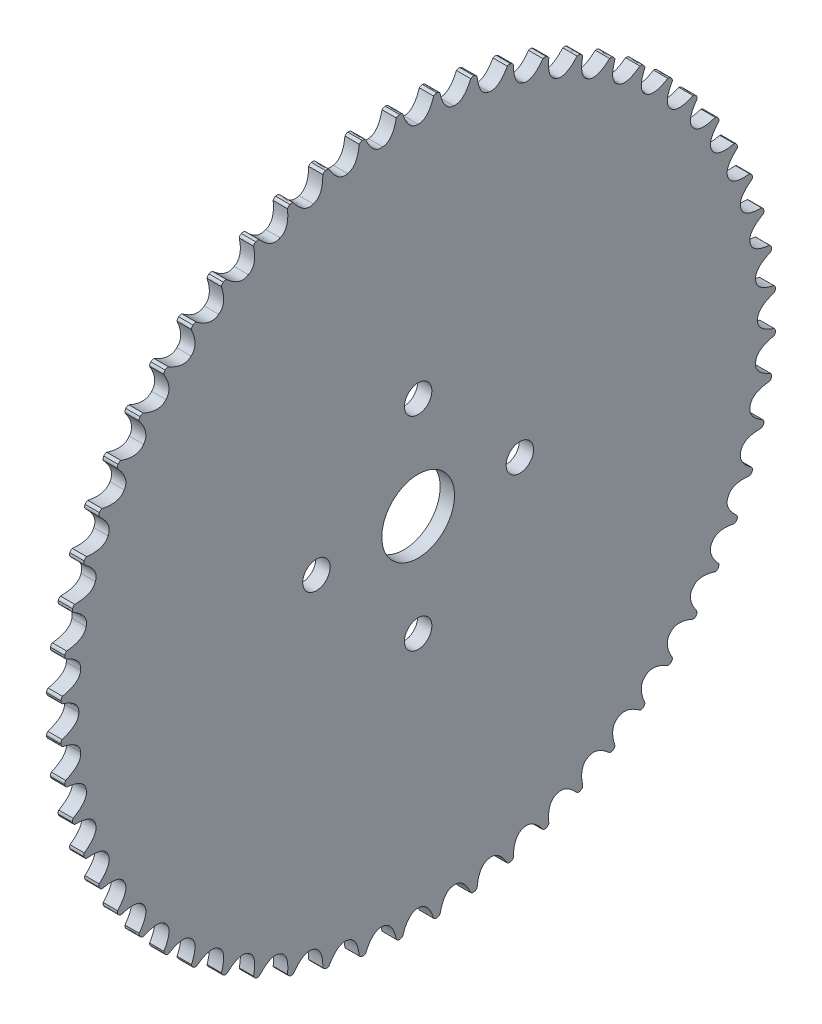
SolidWorks part; units mm, degrees
material "Cast Alloy Steel"
ref_plane "Front Plane" through (0, 0, 0) normal (0, 0, 1) x (1, 0, 0)
ref_plane "Top Plane" through (0, 0, 0) normal (0, 1, 0) x (1, 0, 0)
ref_plane "Right Plane" through (0, 0, 0) normal (1, 0, 0) x (0, 0, -1)
sketch "Sketch2" plane through (0, 0, 0) normal (1, 0, 0) x (0, 0, -1)
  line L3 (-20.5227, 123.2993) -> (-18.5833, 123.6065)
  line L4 (5.5611, 124.8719) -> (7.522, 124.7691)
  line L5 (-7.522, 124.7691) -> (-5.5611, 124.8719)
  line L7 (18.5833, 123.6065) -> (20.5227, 123.2993)
  line L8 (31.4019, 120.9869) -> (33.2986, 120.4787)
  line L9 (43.8765, 117.0417) -> (45.7096, 116.338)
  line L10 (55.8703, 111.8142) -> (57.6199, 110.9228)
  line L11 (67.252, 105.3616) -> (68.8988, 104.2922)
  line L12 (77.8969, 97.7547) -> (79.4229, 96.519)
  line L13 (87.6883, 89.0768) -> (89.0768, 87.6883)
  line L14 (96.519, 79.4229) -> (97.7547, 77.8969)
  line L15 (104.2922, 68.8988) -> (105.3616, 67.252)
  line L16 (110.9228, 57.6199) -> (111.8142, 55.8703)
  line L17 (116.338, 45.7096) -> (117.0417, 43.8765)
  line L18 (120.4787, 33.2986) -> (120.9869, 31.4019)
  line L19 (123.2993, 20.5227) -> (123.6065, 18.5833)
  line L20 (124.7691, 7.522) -> (124.8719, 5.5611)
  line L21 (124.8719, -5.5611) -> (124.7691, -7.522)
  line L22 (123.6065, -18.5833) -> (123.2993, -20.5227)
  line L23 (120.9869, -31.4019) -> (120.4787, -33.2986)
  line L24 (117.0417, -43.8765) -> (116.338, -45.7096)
  line L25 (111.8142, -55.8703) -> (110.9228, -57.6199)
  line L26 (105.3616, -67.252) -> (104.2922, -68.8988)
  line L27 (97.7547, -77.8969) -> (96.519, -79.4229)
  line L28 (89.0768, -87.6883) -> (87.6883, -89.0768)
  line L29 (79.4229, -96.519) -> (77.8969, -97.7547)
  line L30 (68.8988, -104.2922) -> (67.252, -105.3616)
  line L31 (57.6199, -110.9228) -> (55.8703, -111.8142)
  line L32 (45.7096, -116.338) -> (43.8765, -117.0417)
  line L33 (33.2986, -120.4787) -> (31.4019, -120.9869)
  line L34 (20.5227, -123.2993) -> (18.5833, -123.6065)
  line L35 (7.522, -124.7691) -> (5.5611, -124.8719)
  line L36 (-5.5611, -124.8719) -> (-7.522, -124.7691)
  line L37 (-18.5833, -123.6065) -> (-20.5227, -123.2993)
  line L38 (-31.4019, -120.9869) -> (-33.2986, -120.4787)
  line L39 (-43.8765, -117.0417) -> (-45.7096, -116.338)
  line L40 (-55.8703, -111.8142) -> (-57.6199, -110.9228)
  line L41 (-67.252, -105.3616) -> (-68.8988, -104.2922)
  line L42 (-77.8969, -97.7547) -> (-79.4229, -96.519)
  line L43 (-87.6883, -89.0768) -> (-89.0768, -87.6883)
  line L44 (-96.519, -79.4229) -> (-97.7547, -77.8969)
  line L45 (-104.2922, -68.8988) -> (-105.3616, -67.252)
  line L46 (-110.9228, -57.6199) -> (-111.8142, -55.8703)
  line L47 (-116.338, -45.7096) -> (-117.0417, -43.8765)
  line L48 (-120.4787, -33.2986) -> (-120.9869, -31.4019)
  line L49 (-123.2993, -20.5227) -> (-123.6065, -18.5833)
  line L50 (-124.7691, -7.522) -> (-124.8719, -5.5611)
  line L51 (-124.8719, 5.5611) -> (-124.7691, 7.522)
  line L52 (-123.6065, 18.5833) -> (-123.2993, 20.5227)
  line L53 (-120.9869, 31.4019) -> (-120.4787, 33.2986)
  line L54 (-117.0417, 43.8765) -> (-116.338, 45.7096)
  line L55 (-111.8142, 55.8703) -> (-110.9228, 57.6199)
  line L56 (-105.3616, 67.252) -> (-104.2922, 68.8988)
  line L57 (-97.7547, 77.8969) -> (-96.519, 79.4229)
  line L58 (-89.0768, 87.6883) -> (-87.6883, 89.0768)
  line L59 (-79.4229, 96.519) -> (-77.8969, 97.7547)
  line L60 (-68.8988, 104.2922) -> (-67.252, 105.3616)
  line L61 (-57.6199, 110.9228) -> (-55.8703, 111.8142)
  line L62 (-45.7096, 116.338) -> (-43.8765, 117.0417)
  line L63 (-33.2986, 120.4787) -> (-31.4019, 120.9869)
  line L65 (-20.5227, 123.2993) -> (-18.5833, 123.6065) [skipped]
  line L66 (5.5611, 124.8719) -> (7.522, 124.7691) [skipped]
  spline S6 degree 3 poles (-5.5611, 124.8719) (-4.8042, 122.3669) (-3.2326, 118.408) (0, 118.5697) knots 0 0 0 0 1 1 1 1
  spline S7 degree 3 poles (5.5611, 124.8719) (4.8042, 122.3669) (3.2326, 118.408) (0, 118.5697) knots 0 0 0 0 1 1 1 1
  spline S8 degree 3 poles (7.522, 124.7691) (8.0129, 122.1987) (9.1621, 118.0973) (12.3939, 117.9202) knots 0 0 0 0 1 1 1 1
  spline S9 degree 3 poles (18.5833, 123.6065) (17.5687, 121.1944) (15.5919, 117.4215) (12.3939, 117.9202) knots 0 0 0 0 1 1 1 1
  spline S10 degree 3 poles (20.5227, 123.2993) (20.7423, 120.6917) (21.4565, 116.4926) (24.652, 115.9787) knots 0 0 0 0 1 1 1 1
  spline S11 degree 3 poles (31.4019, 120.9869) (30.1407, 118.694) (27.7804, 115.1484) (24.652, 115.9787) knots 0 0 0 0 1 1 1 1
  spline S12 degree 3 poles (33.2986, 120.4787) (33.2444, 117.8624) (33.5157, 113.6116) (36.6401, 112.7665) knots 0 0 0 0 1 1 1 1
  spline S13 degree 3 poles (43.8765, 117.0417) (42.3825, 114.8932) (39.6645, 111.6138) (36.6401, 112.7665) knots 0 0 0 0 1 1 1 1
  spline S14 degree 3 poles (45.7096, 116.338) (45.3822, 113.7418) (45.2078, 109.4859) (48.2266, 108.3188) knots 0 0 0 0 1 1 1 1
  spline S15 degree 3 poles (55.8703, 111.8142) (54.16, 109.8337) (51.114, 106.8563) (48.2266, 108.3188) knots 0 0 0 0 1 1 1 1
  spline S16 degree 3 poles (57.6199, 110.9228) (57.0229, 108.3749) (56.4045, 104.1606) (59.2848, 102.6844) knots 0 0 0 0 1 1 1 1
  spline S17 degree 3 poles (67.252, 105.3616) (65.344, 103.5707) (62.0035, 100.9281) (59.2848, 102.6844) knots 0 0 0 0 1 1 1 1
  spline S18 degree 3 poles (68.8988, 104.2922) (68.0387, 101.8207) (66.9833, 97.6942) (69.6935, 95.9249) knots 0 0 0 0 1 1 1 1
  spline S19 degree 3 poles (77.8969, 97.7547) (75.8122, 96.173) (72.2137, 93.894) (69.6935, 95.9249) knots 0 0 0 0 1 1 1 1
  spline S20 degree 3 poles (79.4229, 96.519) (78.3092, 94.151) (76.8281, 90.1573) (79.3386, 88.1145) knots 0 0 0 0 1 1 1 1
  spline S21 degree 3 poles (87.6883, 89.0768) (85.4497, 87.7217) (81.6327, 85.8313) (79.3386, 88.1145) knots 0 0 0 0 1 1 1 1
  spline S22 degree 3 poles (89.0768, 87.6883) (87.7217, 85.4497) (85.8313, 81.6327) (88.1145, 79.3386) knots 0 0 0 0 1 1 1 1
  spline S23 degree 3 poles (96.519, 79.4229) (94.151, 78.3092) (90.1573, 76.8281) (88.1145, 79.3386) knots 0 0 0 0 1 1 1 1
  spline S24 degree 3 poles (97.7547, 77.8969) (96.173, 75.8122) (93.894, 72.2137) (95.9249, 69.6935) knots 0 0 0 0 1 1 1 1
  spline S25 degree 3 poles (104.2922, 68.8988) (101.8207, 68.0387) (97.6942, 66.9833) (95.9249, 69.6935) knots 0 0 0 0 1 1 1 1
  spline S26 degree 3 poles (105.3616, 67.252) (103.5707, 65.344) (100.9281, 62.0035) (102.6844, 59.2848) knots 0 0 0 0 1 1 1 1
  spline S27 degree 3 poles (110.9228, 57.6199) (108.3749, 57.0229) (104.1606, 56.4045) (102.6844, 59.2848) knots 0 0 0 0 1 1 1 1
  spline S28 degree 3 poles (111.8142, 55.8703) (109.8337, 54.16) (106.8563, 51.114) (108.3188, 48.2266) knots 0 0 0 0 1 1 1 1
  spline S29 degree 3 poles (116.338, 45.7096) (113.7418, 45.3822) (109.4859, 45.2078) (108.3188, 48.2266) knots 0 0 0 0 1 1 1 1
  spline S30 degree 3 poles (117.0417, 43.8765) (114.8932, 42.3825) (111.6138, 39.6645) (112.7665, 36.6401) knots 0 0 0 0 1 1 1 1
  spline S31 degree 3 poles (120.4787, 33.2986) (117.8624, 33.2444) (113.6116, 33.5157) (112.7665, 36.6401) knots 0 0 0 0 1 1 1 1
  spline S32 degree 3 poles (120.9869, 31.4019) (118.694, 30.1407) (115.1484, 27.7804) (115.9787, 24.652) knots 0 0 0 0 1 1 1 1
  spline S33 degree 3 poles (123.2993, 20.5227) (120.6917, 20.7423) (116.4926, 21.4565) (115.9787, 24.652) knots 0 0 0 0 1 1 1 1
  spline S34 degree 3 poles (123.6065, 18.5833) (121.1944, 17.5687) (117.4215, 15.5919) (117.9202, 12.3939) knots 0 0 0 0 1 1 1 1
  spline S35 degree 3 poles (124.7691, 7.522) (122.1987, 8.0129) (118.0973, 9.1621) (117.9202, 12.3939) knots 0 0 0 0 1 1 1 1
  spline S36 degree 3 poles (124.8719, 5.5611) (122.3669, 4.8042) (118.408, 3.2326) (118.5697, 0) knots 0 0 0 0 1 1 1 1
  spline S37 degree 3 poles (124.8719, -5.5611) (122.3669, -4.8042) (118.408, -3.2326) (118.5697, 0) knots 0 0 0 0 1 1 1 1
  spline S38 degree 3 poles (124.7691, -7.522) (122.1987, -8.0129) (118.0973, -9.1621) (117.9202, -12.3939) knots 0 0 0 0 1 1 1 1
  spline S39 degree 3 poles (123.6065, -18.5833) (121.1944, -17.5687) (117.4215, -15.5919) (117.9202, -12.3939) knots 0 0 0 0 1 1 1 1
  spline S40 degree 3 poles (123.2993, -20.5227) (120.6917, -20.7423) (116.4926, -21.4565) (115.9787, -24.652) knots 0 0 0 0 1 1 1 1
  spline S41 degree 3 poles (120.9869, -31.4019) (118.694, -30.1407) (115.1484, -27.7804) (115.9787, -24.652) knots 0 0 0 0 1 1 1 1
  spline S42 degree 3 poles (120.4787, -33.2986) (117.8624, -33.2444) (113.6116, -33.5157) (112.7665, -36.6401) knots 0 0 0 0 1 1 1 1
  spline S43 degree 3 poles (117.0417, -43.8765) (114.8932, -42.3825) (111.6138, -39.6645) (112.7665, -36.6401) knots 0 0 0 0 1 1 1 1
  spline S44 degree 3 poles (116.338, -45.7096) (113.7418, -45.3822) (109.4859, -45.2078) (108.3188, -48.2266) knots 0 0 0 0 1 1 1 1
  spline S45 degree 3 poles (111.8142, -55.8703) (109.8337, -54.16) (106.8563, -51.114) (108.3188, -48.2266) knots 0 0 0 0 1 1 1 1
  spline S46 degree 3 poles (110.9228, -57.6199) (108.3749, -57.0229) (104.1606, -56.4045) (102.6844, -59.2848) knots 0 0 0 0 1 1 1 1
  spline S47 degree 3 poles (105.3616, -67.252) (103.5707, -65.344) (100.9281, -62.0035) (102.6844, -59.2848) knots 0 0 0 0 1 1 1 1
  spline S48 degree 3 poles (104.2922, -68.8988) (101.8207, -68.0387) (97.6942, -66.9833) (95.9249, -69.6935) knots 0 0 0 0 1 1 1 1
  spline S49 degree 3 poles (97.7547, -77.8969) (96.173, -75.8122) (93.894, -72.2137) (95.9249, -69.6935) knots 0 0 0 0 1 1 1 1
  spline S50 degree 3 poles (96.519, -79.4229) (94.151, -78.3092) (90.1573, -76.8281) (88.1145, -79.3386) knots 0 0 0 0 1 1 1 1
  spline S51 degree 3 poles (89.0768, -87.6883) (87.7217, -85.4497) (85.8313, -81.6327) (88.1145, -79.3386) knots 0 0 0 0 1 1 1 1
  spline S52 degree 3 poles (87.6883, -89.0768) (85.4497, -87.7217) (81.6327, -85.8313) (79.3386, -88.1145) knots 0 0 0 0 1 1 1 1
  spline S53 degree 3 poles (79.4229, -96.519) (78.3092, -94.151) (76.8281, -90.1573) (79.3386, -88.1145) knots 0 0 0 0 1 1 1 1
  spline S54 degree 3 poles (77.8969, -97.7547) (75.8122, -96.173) (72.2137, -93.894) (69.6935, -95.9249) knots 0 0 0 0 1 1 1 1
  spline S55 degree 3 poles (68.8988, -104.2922) (68.0387, -101.8207) (66.9833, -97.6942) (69.6935, -95.9249) knots 0 0 0 0 1 1 1 1
  spline S56 degree 3 poles (67.252, -105.3616) (65.344, -103.5707) (62.0035, -100.9281) (59.2848, -102.6844) knots 0 0 0 0 1 1 1 1
  spline S57 degree 3 poles (57.6199, -110.9228) (57.0229, -108.3749) (56.4045, -104.1606) (59.2848, -102.6844) knots 0 0 0 0 1 1 1 1
  spline S58 degree 3 poles (55.8703, -111.8142) (54.16, -109.8337) (51.114, -106.8563) (48.2266, -108.3188) knots 0 0 0 0 1 1 1 1
  spline S59 degree 3 poles (45.7096, -116.338) (45.3822, -113.7418) (45.2078, -109.4859) (48.2266, -108.3188) knots 0 0 0 0 1 1 1 1
  spline S60 degree 3 poles (43.8765, -117.0417) (42.3825, -114.8932) (39.6645, -111.6138) (36.6401, -112.7665) knots 0 0 0 0 1 1 1 1
  spline S61 degree 3 poles (33.2986, -120.4787) (33.2444, -117.8624) (33.5157, -113.6116) (36.6401, -112.7665) knots 0 0 0 0 1 1 1 1
  spline S62 degree 3 poles (31.4019, -120.9869) (30.1407, -118.694) (27.7804, -115.1484) (24.652, -115.9787) knots 0 0 0 0 1 1 1 1
  spline S63 degree 3 poles (20.5227, -123.2993) (20.7423, -120.6917) (21.4565, -116.4926) (24.652, -115.9787) knots 0 0 0 0 1 1 1 1
  spline S64 degree 3 poles (18.5833, -123.6065) (17.5687, -121.1944) (15.5919, -117.4215) (12.3939, -117.9202) knots 0 0 0 0 1 1 1 1
  spline S65 degree 3 poles (7.522, -124.7691) (8.0129, -122.1987) (9.1621, -118.0973) (12.3939, -117.9202) knots 0 0 0 0 1 1 1 1
  spline S66 degree 3 poles (5.5611, -124.8719) (4.8042, -122.3669) (3.2326, -118.408) (0, -118.5697) knots 0 0 0 0 1 1 1 1
  spline S67 degree 3 poles (-5.5611, -124.8719) (-4.8042, -122.3669) (-3.2326, -118.408) (0, -118.5697) knots 0 0 0 0 1 1 1 1
  spline S68 degree 3 poles (-7.522, -124.7691) (-8.0129, -122.1987) (-9.1621, -118.0973) (-12.3939, -117.9202) knots 0 0 0 0 1 1 1 1
  spline S69 degree 3 poles (-18.5833, -123.6065) (-17.5687, -121.1944) (-15.5919, -117.4215) (-12.3939, -117.9202) knots 0 0 0 0 1 1 1 1
  spline S70 degree 3 poles (-20.5227, -123.2993) (-20.7423, -120.6917) (-21.4565, -116.4926) (-24.652, -115.9787) knots 0 0 0 0 1 1 1 1
  spline S71 degree 3 poles (-31.4019, -120.9869) (-30.1407, -118.694) (-27.7804, -115.1484) (-24.652, -115.9787) knots 0 0 0 0 1 1 1 1
  spline S72 degree 3 poles (-33.2986, -120.4787) (-33.2444, -117.8624) (-33.5157, -113.6116) (-36.6401, -112.7665) knots 0 0 0 0 1 1 1 1
  spline S73 degree 3 poles (-43.8765, -117.0417) (-42.3825, -114.8932) (-39.6645, -111.6138) (-36.6401, -112.7665) knots 0 0 0 0 1 1 1 1
  spline S74 degree 3 poles (-45.7096, -116.338) (-45.3822, -113.7418) (-45.2078, -109.4859) (-48.2266, -108.3188) knots 0 0 0 0 1 1 1 1
  spline S75 degree 3 poles (-55.8703, -111.8142) (-54.16, -109.8337) (-51.114, -106.8563) (-48.2266, -108.3188) knots 0 0 0 0 1 1 1 1
  spline S76 degree 3 poles (-57.6199, -110.9228) (-57.0229, -108.3749) (-56.4045, -104.1606) (-59.2848, -102.6844) knots 0 0 0 0 1 1 1 1
  spline S77 degree 3 poles (-67.252, -105.3616) (-65.344, -103.5707) (-62.0035, -100.9281) (-59.2848, -102.6844) knots 0 0 0 0 1 1 1 1
  spline S78 degree 3 poles (-68.8988, -104.2922) (-68.0387, -101.8207) (-66.9833, -97.6942) (-69.6935, -95.9249) knots 0 0 0 0 1 1 1 1
  spline S79 degree 3 poles (-77.8969, -97.7547) (-75.8122, -96.173) (-72.2137, -93.894) (-69.6935, -95.9249) knots 0 0 0 0 1 1 1 1
  spline S80 degree 3 poles (-79.4229, -96.519) (-78.3092, -94.151) (-76.8281, -90.1573) (-79.3386, -88.1145) knots 0 0 0 0 1 1 1 1
  spline S81 degree 3 poles (-87.6883, -89.0768) (-85.4497, -87.7217) (-81.6327, -85.8313) (-79.3386, -88.1145) knots 0 0 0 0 1 1 1 1
  spline S82 degree 3 poles (-89.0768, -87.6883) (-87.7217, -85.4497) (-85.8313, -81.6327) (-88.1145, -79.3386) knots 0 0 0 0 1 1 1 1
  spline S83 degree 3 poles (-96.519, -79.4229) (-94.151, -78.3092) (-90.1573, -76.8281) (-88.1145, -79.3386) knots 0 0 0 0 1 1 1 1
  spline S84 degree 3 poles (-97.7547, -77.8969) (-96.173, -75.8122) (-93.894, -72.2137) (-95.9249, -69.6935) knots 0 0 0 0 1 1 1 1
  spline S85 degree 3 poles (-104.2922, -68.8988) (-101.8207, -68.0387) (-97.6942, -66.9833) (-95.9249, -69.6935) knots 0 0 0 0 1 1 1 1
  spline S86 degree 3 poles (-105.3616, -67.252) (-103.5707, -65.344) (-100.9281, -62.0035) (-102.6844, -59.2848) knots 0 0 0 0 1 1 1 1
  spline S87 degree 3 poles (-110.9228, -57.6199) (-108.3749, -57.0229) (-104.1606, -56.4045) (-102.6844, -59.2848) knots 0 0 0 0 1 1 1 1
  spline S88 degree 3 poles (-111.8142, -55.8703) (-109.8337, -54.16) (-106.8563, -51.114) (-108.3188, -48.2266) knots 0 0 0 0 1 1 1 1
  spline S89 degree 3 poles (-116.338, -45.7096) (-113.7418, -45.3822) (-109.4859, -45.2078) (-108.3188, -48.2266) knots 0 0 0 0 1 1 1 1
  spline S90 degree 3 poles (-117.0417, -43.8765) (-114.8932, -42.3825) (-111.6138, -39.6645) (-112.7665, -36.6401) knots 0 0 0 0 1 1 1 1
  spline S91 degree 3 poles (-120.4787, -33.2986) (-117.8624, -33.2444) (-113.6116, -33.5157) (-112.7665, -36.6401) knots 0 0 0 0 1 1 1 1
  spline S92 degree 3 poles (-120.9869, -31.4019) (-118.694, -30.1407) (-115.1484, -27.7804) (-115.9787, -24.652) knots 0 0 0 0 1 1 1 1
  spline S93 degree 3 poles (-123.2993, -20.5227) (-120.6917, -20.7423) (-116.4926, -21.4565) (-115.9787, -24.652) knots 0 0 0 0 1 1 1 1
  spline S94 degree 3 poles (-123.6065, -18.5833) (-121.1944, -17.5687) (-117.4215, -15.5919) (-117.9202, -12.3939) knots 0 0 0 0 1 1 1 1
  spline S95 degree 3 poles (-124.7691, -7.522) (-122.1987, -8.0129) (-118.0973, -9.1621) (-117.9202, -12.3939) knots 0 0 0 0 1 1 1 1
  spline S96 degree 3 poles (-124.8719, -5.5611) (-122.3669, -4.8042) (-118.408, -3.2326) (-118.5697, 0) knots 0 0 0 0 1 1 1 1
  spline S97 degree 3 poles (-124.8719, 5.5611) (-122.3669, 4.8042) (-118.408, 3.2326) (-118.5697, 0) knots 0 0 0 0 1 1 1 1
  spline S98 degree 3 poles (-124.7691, 7.522) (-122.1987, 8.0129) (-118.0973, 9.1621) (-117.9202, 12.3939) knots 0 0 0 0 1 1 1 1
  spline S99 degree 3 poles (-123.6065, 18.5833) (-121.1944, 17.5687) (-117.4215, 15.5919) (-117.9202, 12.3939) knots 0 0 0 0 1 1 1 1
  spline S100 degree 3 poles (-123.2993, 20.5227) (-120.6917, 20.7423) (-116.4926, 21.4565) (-115.9787, 24.652) knots 0 0 0 0 1 1 1 1
  spline S101 degree 3 poles (-120.9869, 31.4019) (-118.694, 30.1407) (-115.1484, 27.7804) (-115.9787, 24.652) knots 0 0 0 0 1 1 1 1
  spline S102 degree 3 poles (-120.4787, 33.2986) (-117.8624, 33.2444) (-113.6116, 33.5157) (-112.7665, 36.6401) knots 0 0 0 0 1 1 1 1
  spline S103 degree 3 poles (-117.0417, 43.8765) (-114.8932, 42.3825) (-111.6138, 39.6645) (-112.7665, 36.6401) knots 0 0 0 0 1 1 1 1
  spline S104 degree 3 poles (-116.338, 45.7096) (-113.7418, 45.3822) (-109.4859, 45.2078) (-108.3188, 48.2266) knots 0 0 0 0 1 1 1 1
  spline S105 degree 3 poles (-111.8142, 55.8703) (-109.8337, 54.16) (-106.8563, 51.114) (-108.3188, 48.2266) knots 0 0 0 0 1 1 1 1
  spline S106 degree 3 poles (-110.9228, 57.6199) (-108.3749, 57.0229) (-104.1606, 56.4045) (-102.6844, 59.2848) knots 0 0 0 0 1 1 1 1
  spline S107 degree 3 poles (-105.3616, 67.252) (-103.5707, 65.344) (-100.9281, 62.0035) (-102.6844, 59.2848) knots 0 0 0 0 1 1 1 1
  spline S108 degree 3 poles (-104.2922, 68.8988) (-101.8207, 68.0387) (-97.6942, 66.9833) (-95.9249, 69.6935) knots 0 0 0 0 1 1 1 1
  spline S109 degree 3 poles (-97.7547, 77.8969) (-96.173, 75.8122) (-93.894, 72.2137) (-95.9249, 69.6935) knots 0 0 0 0 1 1 1 1
  spline S110 degree 3 poles (-96.519, 79.4229) (-94.151, 78.3092) (-90.1573, 76.8281) (-88.1145, 79.3386) knots 0 0 0 0 1 1 1 1
  spline S111 degree 3 poles (-89.0768, 87.6883) (-87.7217, 85.4497) (-85.8313, 81.6327) (-88.1145, 79.3386) knots 0 0 0 0 1 1 1 1
  spline S112 degree 3 poles (-87.6883, 89.0768) (-85.4497, 87.7217) (-81.6327, 85.8313) (-79.3386, 88.1145) knots 0 0 0 0 1 1 1 1
  spline S113 degree 3 poles (-79.4229, 96.519) (-78.3092, 94.151) (-76.8281, 90.1573) (-79.3386, 88.1145) knots 0 0 0 0 1 1 1 1
  spline S114 degree 3 poles (-77.8969, 97.7547) (-75.8122, 96.173) (-72.2137, 93.894) (-69.6935, 95.9249) knots 0 0 0 0 1 1 1 1
  spline S115 degree 3 poles (-68.8988, 104.2922) (-68.0387, 101.8207) (-66.9833, 97.6942) (-69.6935, 95.9249) knots 0 0 0 0 1 1 1 1
  spline S116 degree 3 poles (-67.252, 105.3616) (-65.344, 103.5707) (-62.0035, 100.9281) (-59.2848, 102.6844) knots 0 0 0 0 1 1 1 1
  spline S117 degree 3 poles (-57.6199, 110.9228) (-57.0229, 108.3749) (-56.4045, 104.1606) (-59.2848, 102.6844) knots 0 0 0 0 1 1 1 1
  spline S118 degree 3 poles (-55.8703, 111.8142) (-54.16, 109.8337) (-51.114, 106.8563) (-48.2266, 108.3188) knots 0 0 0 0 1 1 1 1
  spline S119 degree 3 poles (-45.7096, 116.338) (-45.3822, 113.7418) (-45.2078, 109.4859) (-48.2266, 108.3188) knots 0 0 0 0 1 1 1 1
  spline S120 degree 3 poles (-43.8765, 117.0417) (-42.3825, 114.8932) (-39.6645, 111.6138) (-36.6401, 112.7665) knots 0 0 0 0 1 1 1 1
  spline S121 degree 3 poles (-33.2986, 120.4787) (-33.2444, 117.8624) (-33.5157, 113.6116) (-36.6401, 112.7665) knots 0 0 0 0 1 1 1 1
  spline S122 degree 3 poles (-31.4019, 120.9869) (-30.1407, 118.694) (-27.7804, 115.1484) (-24.652, 115.9787) knots 0 0 0 0 1 1 1 1
  spline S123 degree 3 poles (-20.5227, 123.2993) (-20.7423, 120.6917) (-21.4565, 116.4926) (-24.652, 115.9787) knots 0 0 0 0 1 1 1 1
  spline S124 degree 3 poles (-18.5833, 123.6065) (-17.5687, 121.1944) (-15.5919, 117.4215) (-12.3939, 117.9202) knots 0 0 0 0 1 1 1 1
  spline S125 degree 3 poles (-7.522, 124.7691) (-8.0129, 122.1987) (-9.1621, 118.0973) (-12.3939, 117.9202) knots 0 0 0 0 1 1 1 1
  dimension "D1" = 60
extrude "Boss-Extrude1" add sketch "Sketch2" along normal blind 5
sketch "Sketch3" plane through (0, 0, 0) normal (-1, 0, 0) x (0, 0, 1)
  line L0 (-97.4272, 77.3808) -> (-97.8023, 77.9718)
  line L1 (-97.8023, 77.9718) -> (-96.6022, 79.4538)
  line L2 (-87.7678, 89.1162) -> (-87.1408, 88.805)
  line L3 (-89.1162, 87.7678) -> (-87.7678, 89.1162)
  line L4 (-96.6022, 79.4538) -> (-95.9461, 79.2098)
  line L5 (-88.805, 87.1408) -> (-89.1162, 87.7678)
  line L6 (-77.9718, 97.8023) -> (-77.3808, 97.4272)
  line L7 (-79.4538, 96.6022) -> (-77.9718, 97.8023)
  line L8 (-79.2098, 95.9461) -> (-79.4538, 96.6022)
  line L9 (-67.3216, 105.4168) -> (-66.773, 104.982)
  line L10 (-68.9209, 104.3782) -> (-67.3216, 105.4168)
  line L11 (-68.7468, 103.7001) -> (-68.9209, 104.3782)
  line L12 (-55.9337, 111.8763) -> (-55.4336, 111.3865)
  line L13 (-57.6328, 111.0106) -> (-55.9337, 111.8763)
  line L14 (-57.5306, 110.3181) -> (-57.6328, 111.0106)
  line L15 (-43.933, 117.1101) -> (-43.4868, 116.5707)
  line L16 (-45.7133, 116.4267) -> (-43.933, 117.1101)
  line L17 (-45.684, 115.7273) -> (-45.7133, 116.4267)
  line L18 (-31.451, 121.0608) -> (-31.0636, 120.4778)
  line L19 (-33.293, 120.5672) -> (-31.451, 121.0608)
  line L20 (-33.337, 119.8686) -> (-33.293, 120.5672)
  line L21 (-18.6244, 123.6851) -> (-18.3001, 123.0648)
  line L22 (-20.5079, 123.3868) -> (-18.6244, 123.6851)
  line L23 (-20.6247, 122.6966) -> (-20.5079, 123.3868)
  line L24 (-5.5938, 124.9544) -> (-5.3361, 124.3035)
  line L25 (-7.4981, 124.8546) -> (-5.5938, 124.9544)
  line L26 (-7.6864, 124.1804) -> (-7.4981, 124.8546)
  line L27 (7.4981, 124.8546) -> (7.6864, 124.1804)
  line L28 (5.5938, 124.9544) -> (7.4981, 124.8546)
  line L29 (5.3361, 124.3035) -> (5.5938, 124.9544)
  line L30 (20.5079, 123.3868) -> (20.6247, 122.6966)
  line L31 (18.6244, 123.6851) -> (20.5079, 123.3868)
  line L32 (18.3001, 123.0648) -> (18.6244, 123.6851)
  line L33 (33.293, 120.5672) -> (33.337, 119.8686)
  line L34 (31.451, 121.0608) -> (33.293, 120.5672)
  line L35 (31.0636, 120.4778) -> (31.451, 121.0608)
  line L36 (45.7133, 116.4267) -> (45.684, 115.7273)
  line L37 (43.933, 117.1101) -> (45.7133, 116.4267)
  line L38 (43.4868, 116.5707) -> (43.933, 117.1101)
  line L39 (57.6328, 111.0106) -> (57.5306, 110.3181)
  line L40 (55.9337, 111.8763) -> (57.6328, 111.0106)
  line L41 (55.4336, 111.3865) -> (55.9337, 111.8763)
  line L42 (68.9209, 104.3782) -> (68.7468, 103.7001)
  line L43 (67.3216, 105.4168) -> (68.9209, 104.3782)
  line L44 (66.773, 104.982) -> (67.3216, 105.4168)
  line L45 (79.4538, 96.6022) -> (79.2098, 95.9461)
  line L46 (77.9718, 97.8023) -> (79.4538, 96.6022)
  line L47 (77.3808, 97.4272) -> (77.9718, 97.8023)
  line L48 (89.1162, 87.7678) -> (88.805, 87.1408)
  line L49 (87.7678, 89.1162) -> (89.1162, 87.7678)
  line L50 (87.1408, 88.805) -> (87.7678, 89.1162)
  line L51 (97.8023, 77.9718) -> (97.4272, 77.3808)
  line L52 (96.6022, 79.4538) -> (97.8023, 77.9718)
  line L53 (95.9461, 79.2098) -> (96.6022, 79.4538)
  line L54 (105.4168, 67.3216) -> (104.982, 66.773)
  line L55 (104.3782, 68.9209) -> (105.4168, 67.3216)
  line L56 (103.7001, 68.7468) -> (104.3782, 68.9209)
  line L57 (111.8763, 55.9337) -> (111.3865, 55.4336)
  line L58 (111.0106, 57.6328) -> (111.8763, 55.9337)
  line L59 (110.3181, 57.5306) -> (111.0106, 57.6328)
  line L60 (117.1101, 43.933) -> (116.5707, 43.4868)
  line L61 (116.4267, 45.7133) -> (117.1101, 43.933)
  line L62 (115.7273, 45.684) -> (116.4267, 45.7133)
  line L63 (121.0608, 31.451) -> (120.4778, 31.0636)
  line L64 (120.5672, 33.293) -> (121.0608, 31.451)
  line L65 (119.8686, 33.337) -> (120.5672, 33.293)
  line L66 (123.6851, 18.6244) -> (123.0648, 18.3001)
  line L67 (123.3868, 20.5079) -> (123.6851, 18.6244)
  line L68 (122.6966, 20.6247) -> (123.3868, 20.5079)
  line L69 (124.9544, 5.5938) -> (124.3035, 5.3361)
  line L70 (124.8546, 7.4981) -> (124.9544, 5.5938)
  line L71 (124.1804, 7.6864) -> (124.8546, 7.4981)
  line L72 (124.8546, -7.4981) -> (124.1804, -7.6864)
  line L73 (124.9544, -5.5938) -> (124.8546, -7.4981)
  line L74 (124.3035, -5.3361) -> (124.9544, -5.5938)
  line L75 (123.3868, -20.5079) -> (122.6966, -20.6247)
  line L76 (123.6851, -18.6244) -> (123.3868, -20.5079)
  line L77 (123.0648, -18.3001) -> (123.6851, -18.6244)
  line L78 (120.5672, -33.293) -> (119.8686, -33.337)
  line L79 (121.0608, -31.451) -> (120.5672, -33.293)
  line L80 (120.4778, -31.0636) -> (121.0608, -31.451)
  line L81 (116.4267, -45.7133) -> (115.7273, -45.684)
  line L82 (117.1101, -43.933) -> (116.4267, -45.7133)
  line L83 (116.5707, -43.4868) -> (117.1101, -43.933)
  line L84 (111.0106, -57.6328) -> (110.3181, -57.5306)
  line L85 (111.8763, -55.9337) -> (111.0106, -57.6328)
  line L86 (111.3865, -55.4336) -> (111.8763, -55.9337)
  line L87 (104.3782, -68.9209) -> (103.7001, -68.7468)
  line L88 (105.4168, -67.3216) -> (104.3782, -68.9209)
  line L89 (104.982, -66.773) -> (105.4168, -67.3216)
  line L90 (96.6022, -79.4538) -> (95.9461, -79.2098)
  line L91 (97.8023, -77.9718) -> (96.6022, -79.4538)
  line L92 (97.4272, -77.3808) -> (97.8023, -77.9718)
  line L93 (87.7678, -89.1162) -> (87.1408, -88.805)
  line L94 (89.1162, -87.7678) -> (87.7678, -89.1162)
  line L95 (88.805, -87.1408) -> (89.1162, -87.7678)
  line L96 (77.9718, -97.8023) -> (77.3808, -97.4272)
  line L97 (79.4538, -96.6022) -> (77.9718, -97.8023)
  line L98 (79.2098, -95.9461) -> (79.4538, -96.6022)
  line L99 (67.3216, -105.4168) -> (66.773, -104.982)
  line L100 (68.9209, -104.3782) -> (67.3216, -105.4168)
  line L101 (68.7468, -103.7001) -> (68.9209, -104.3782)
  line L102 (55.9337, -111.8763) -> (55.4336, -111.3865)
  line L103 (57.6328, -111.0106) -> (55.9337, -111.8763)
  line L104 (57.5306, -110.3181) -> (57.6328, -111.0106)
  line L105 (43.933, -117.1101) -> (43.4868, -116.5707)
  line L106 (45.7133, -116.4267) -> (43.933, -117.1101)
  line L107 (45.684, -115.7273) -> (45.7133, -116.4267)
  line L108 (31.451, -121.0608) -> (31.0636, -120.4778)
  line L109 (33.293, -120.5672) -> (31.451, -121.0608)
  line L110 (33.337, -119.8686) -> (33.293, -120.5672)
  line L111 (18.6244, -123.6851) -> (18.3001, -123.0648)
  line L112 (20.5079, -123.3868) -> (18.6244, -123.6851)
  line L113 (20.6247, -122.6966) -> (20.5079, -123.3868)
  line L114 (5.5938, -124.9544) -> (5.3361, -124.3035)
  line L115 (7.4981, -124.8546) -> (5.5938, -124.9544)
  line L116 (7.6864, -124.1804) -> (7.4981, -124.8546)
  line L117 (-7.4981, -124.8546) -> (-7.6864, -124.1804)
  line L118 (-5.5938, -124.9544) -> (-7.4981, -124.8546)
  line L119 (-5.3361, -124.3035) -> (-5.5938, -124.9544)
  line L120 (-20.5079, -123.3868) -> (-20.6247, -122.6966)
  line L121 (-18.6244, -123.6851) -> (-20.5079, -123.3868)
  line L122 (-18.3001, -123.0648) -> (-18.6244, -123.6851)
  line L123 (-33.293, -120.5672) -> (-33.337, -119.8686)
  line L124 (-31.451, -121.0608) -> (-33.293, -120.5672)
  line L125 (-31.0636, -120.4778) -> (-31.451, -121.0608)
  line L126 (-45.7133, -116.4267) -> (-45.684, -115.7273)
  line L127 (-43.933, -117.1101) -> (-45.7133, -116.4267)
  line L128 (-43.4868, -116.5707) -> (-43.933, -117.1101)
  line L129 (-57.6328, -111.0106) -> (-57.5306, -110.3181)
  line L130 (-55.9337, -111.8763) -> (-57.6328, -111.0106)
  line L131 (-55.4336, -111.3865) -> (-55.9337, -111.8763)
  line L132 (-68.9209, -104.3782) -> (-68.7468, -103.7001)
  line L133 (-67.3216, -105.4168) -> (-68.9209, -104.3782)
  line L134 (-66.773, -104.982) -> (-67.3216, -105.4168)
  line L135 (-79.4538, -96.6022) -> (-79.2098, -95.9461)
  line L136 (-77.9718, -97.8023) -> (-79.4538, -96.6022)
  line L137 (-77.3808, -97.4272) -> (-77.9718, -97.8023)
  line L138 (-89.1162, -87.7678) -> (-88.805, -87.1408)
  line L139 (-87.7678, -89.1162) -> (-89.1162, -87.7678)
  line L140 (-87.1408, -88.805) -> (-87.7678, -89.1162)
  line L141 (-97.8023, -77.9718) -> (-97.4272, -77.3808)
  line L142 (-96.6022, -79.4538) -> (-97.8023, -77.9718)
  line L143 (-95.9461, -79.2098) -> (-96.6022, -79.4538)
  line L144 (-105.4168, -67.3216) -> (-104.982, -66.773)
  line L145 (-104.3782, -68.9209) -> (-105.4168, -67.3216)
  line L146 (-103.7001, -68.7468) -> (-104.3782, -68.9209)
  line L147 (-111.8763, -55.9337) -> (-111.3865, -55.4336)
  line L148 (-111.0106, -57.6328) -> (-111.8763, -55.9337)
  line L149 (-110.3181, -57.5306) -> (-111.0106, -57.6328)
  line L150 (-117.1101, -43.933) -> (-116.5707, -43.4868)
  line L151 (-116.4267, -45.7133) -> (-117.1101, -43.933)
  line L152 (-115.7273, -45.684) -> (-116.4267, -45.7133)
  line L153 (-121.0608, -31.451) -> (-120.4778, -31.0636)
  line L154 (-120.5672, -33.293) -> (-121.0608, -31.451)
  line L155 (-119.8686, -33.337) -> (-120.5672, -33.293)
  line L156 (-123.6851, -18.6244) -> (-123.0648, -18.3001)
  line L157 (-123.3868, -20.5079) -> (-123.6851, -18.6244)
  line L158 (-122.6966, -20.6247) -> (-123.3868, -20.5079)
  line L159 (-124.9544, -5.5938) -> (-124.3035, -5.3361)
  line L160 (-124.8546, -7.4981) -> (-124.9544, -5.5938)
  line L161 (-124.1804, -7.6864) -> (-124.8546, -7.4981)
  line L162 (-124.8546, 7.4981) -> (-124.1804, 7.6864)
  line L163 (-124.9544, 5.5938) -> (-124.8546, 7.4981)
  line L164 (-124.3035, 5.3361) -> (-124.9544, 5.5938)
  line L165 (-123.3868, 20.5079) -> (-122.6966, 20.6247)
  line L166 (-123.6851, 18.6244) -> (-123.3868, 20.5079)
  line L167 (-123.0648, 18.3001) -> (-123.6851, 18.6244)
  line L168 (-120.5672, 33.293) -> (-119.8686, 33.337)
  line L169 (-121.0608, 31.451) -> (-120.5672, 33.293)
  line L170 (-120.4778, 31.0636) -> (-121.0608, 31.451)
  line L171 (-116.4267, 45.7133) -> (-115.7273, 45.684)
  line L172 (-117.1101, 43.933) -> (-116.4267, 45.7133)
  line L173 (-116.5707, 43.4868) -> (-117.1101, 43.933)
  line L174 (-111.0106, 57.6328) -> (-110.3181, 57.5306)
  line L175 (-111.8763, 55.9337) -> (-111.0106, 57.6328)
  line L176 (-111.3865, 55.4336) -> (-111.8763, 55.9337)
  line L177 (-104.3782, 68.9209) -> (-103.7001, 68.7468)
  line L178 (-105.4168, 67.3216) -> (-104.3782, 68.9209)
  line L179 (-104.982, 66.773) -> (-105.4168, 67.3216)
  spline S0 degree 2 poles (-97.4272, 77.3808) (-97.6062, 78.0463) (-97.1369, 78.6599) knots 0 0 0 1 1 1
  spline S1 degree 2 poles (-88.805, 87.1408) (-88.9134, 87.8213) (-88.3825, 88.3825) knots 0 0 0 1 1 1
  spline S2 degree 2 poles (-95.9461, 79.2098) (-96.6342, 79.2465) (-97.1369, 78.6599) knots 0 0 0 1 1 1
  spline S3 degree 2 poles (-87.1408, 88.805) (-87.8213, 88.9134) (-88.3825, 88.3825) knots 0 0 0 1 1 1
  spline S4 degree 2 poles (-79.2098, 95.9461) (-79.2465, 96.6342) (-78.6599, 97.1369) knots 0 0 0 1 1 1
  spline S5 degree 2 poles (-77.3808, 97.4272) (-78.0463, 97.6062) (-78.6599, 97.1369) knots 0 0 0 1 1 1
  spline S6 degree 2 poles (-68.7468, 103.7001) (-68.7114, 104.3884) (-68.0754, 104.8269) knots 0 0 0 1 1 1
  spline S7 degree 2 poles (-66.773, 104.982) (-67.4161, 105.2295) (-68.0754, 104.8269) knots 0 0 0 1 1 1
  spline S8 degree 2 poles (-57.5306, 110.3181) (-57.4234, 110.9988) (-56.7451, 111.3685) knots 0 0 0 1 1 1
  spline S9 degree 2 poles (-55.4336, 111.3865) (-56.0473, 111.7) (-56.7451, 111.3685) knots 0 0 0 1 1 1
  spline S10 degree 2 poles (-45.684, 115.7273) (-45.5063, 116.3931) (-44.793, 116.6899) knots 0 0 0 1 1 1
  spline S11 degree 2 poles (-43.4868, 116.5707) (-44.0644, 116.9466) (-44.793, 116.6899) knots 0 0 0 1 1 1
  spline S12 degree 2 poles (-33.337, 119.8686) (-33.0906, 120.5122) (-32.3503, 120.7328) knots 0 0 0 1 1 1
  spline S13 degree 2 poles (-31.0636, 120.4778) (-31.5988, 120.912) (-32.3503, 120.7328) knots 0 0 0 1 1 1
  spline S14 degree 2 poles (-20.6247, 122.6966) (-20.3124, 123.311) (-19.553, 123.4529) knots 0 0 0 1 1 1
  spline S15 degree 2 poles (-18.3001, 123.0648) (-18.7869, 123.5526) (-19.553, 123.4529) knots 0 0 0 1 1 1
  spline S16 degree 2 poles (-7.6864, 124.1804) (-7.3116, 124.7587) (-6.5416, 124.8205) knots 0 0 0 1 1 1
  spline S17 degree 2 poles (-5.3361, 124.3035) (-5.7693, 124.8395) (-6.5416, 124.8205) knots 0 0 0 1 1 1
  spline S18 degree 2 poles (5.3361, 124.3035) (5.7693, 124.8395) (6.5416, 124.8205) knots 0 0 0 1 1 1
  spline S19 degree 2 poles (7.6864, 124.1804) (7.3116, 124.7587) (6.5416, 124.8205) knots 0 0 0 1 1 1
  spline S20 degree 2 poles (18.3001, 123.0648) (18.7869, 123.5526) (19.553, 123.4529) knots 0 0 0 1 1 1
  spline S21 degree 2 poles (20.6247, 122.6966) (20.3124, 123.311) (19.553, 123.4529) knots 0 0 0 1 1 1
  spline S22 degree 2 poles (31.0636, 120.4778) (31.5988, 120.912) (32.3503, 120.7328) knots 0 0 0 1 1 1
  spline S23 degree 2 poles (33.337, 119.8686) (33.0906, 120.5122) (32.3503, 120.7328) knots 0 0 0 1 1 1
  spline S24 degree 2 poles (43.4868, 116.5707) (44.0644, 116.9466) (44.793, 116.6899) knots 0 0 0 1 1 1
  spline S25 degree 2 poles (45.684, 115.7273) (45.5063, 116.3931) (44.793, 116.6899) knots 0 0 0 1 1 1
  spline S26 degree 2 poles (55.4336, 111.3865) (56.0473, 111.7) (56.7451, 111.3685) knots 0 0 0 1 1 1
  spline S27 degree 2 poles (57.5306, 110.3181) (57.4234, 110.9988) (56.7451, 111.3685) knots 0 0 0 1 1 1
  spline S28 degree 2 poles (66.773, 104.982) (67.4161, 105.2295) (68.0754, 104.8269) knots 0 0 0 1 1 1
  spline S29 degree 2 poles (68.7468, 103.7001) (68.7114, 104.3884) (68.0754, 104.8269) knots 0 0 0 1 1 1
  spline S30 degree 2 poles (77.3808, 97.4272) (78.0463, 97.6062) (78.6599, 97.1369) knots 0 0 0 1 1 1
  spline S31 degree 2 poles (79.2098, 95.9461) (79.2465, 96.6342) (78.6599, 97.1369) knots 0 0 0 1 1 1
  spline S32 degree 2 poles (87.1408, 88.805) (87.8213, 88.9134) (88.3825, 88.3825) knots 0 0 0 1 1 1
  spline S33 degree 2 poles (88.805, 87.1408) (88.9134, 87.8213) (88.3825, 88.3825) knots 0 0 0 1 1 1
  spline S34 degree 2 poles (95.9461, 79.2098) (96.6342, 79.2465) (97.1369, 78.6599) knots 0 0 0 1 1 1
  spline S35 degree 2 poles (97.4272, 77.3808) (97.6062, 78.0463) (97.1369, 78.6599) knots 0 0 0 1 1 1
  spline S36 degree 2 poles (103.7001, 68.7468) (104.3884, 68.7114) (104.8269, 68.0754) knots 0 0 0 1 1 1
  spline S37 degree 2 poles (104.982, 66.773) (105.2295, 67.4161) (104.8269, 68.0754) knots 0 0 0 1 1 1
  spline S38 degree 2 poles (110.3181, 57.5306) (110.9988, 57.4234) (111.3685, 56.7451) knots 0 0 0 1 1 1
  spline S39 degree 2 poles (111.3865, 55.4336) (111.7, 56.0473) (111.3685, 56.7451) knots 0 0 0 1 1 1
  spline S40 degree 2 poles (115.7273, 45.684) (116.3931, 45.5063) (116.6899, 44.793) knots 0 0 0 1 1 1
  spline S41 degree 2 poles (116.5707, 43.4868) (116.9466, 44.0644) (116.6899, 44.793) knots 0 0 0 1 1 1
  spline S42 degree 2 poles (119.8686, 33.337) (120.5122, 33.0906) (120.7328, 32.3503) knots 0 0 0 1 1 1
  spline S43 degree 2 poles (120.4778, 31.0636) (120.912, 31.5988) (120.7328, 32.3503) knots 0 0 0 1 1 1
  spline S44 degree 2 poles (122.6966, 20.6247) (123.311, 20.3124) (123.4529, 19.553) knots 0 0 0 1 1 1
  spline S45 degree 2 poles (123.0648, 18.3001) (123.5526, 18.7869) (123.4529, 19.553) knots 0 0 0 1 1 1
  spline S46 degree 2 poles (124.1804, 7.6864) (124.7587, 7.3116) (124.8205, 6.5416) knots 0 0 0 1 1 1
  spline S47 degree 2 poles (124.3035, 5.3361) (124.8395, 5.7693) (124.8205, 6.5416) knots 0 0 0 1 1 1
  spline S48 degree 2 poles (124.3035, -5.3361) (124.8395, -5.7693) (124.8205, -6.5416) knots 0 0 0 1 1 1
  spline S49 degree 2 poles (124.1804, -7.6864) (124.7587, -7.3116) (124.8205, -6.5416) knots 0 0 0 1 1 1
  spline S50 degree 2 poles (123.0648, -18.3001) (123.5526, -18.7869) (123.4529, -19.553) knots 0 0 0 1 1 1
  spline S51 degree 2 poles (122.6966, -20.6247) (123.311, -20.3124) (123.4529, -19.553) knots 0 0 0 1 1 1
  spline S52 degree 2 poles (120.4778, -31.0636) (120.912, -31.5988) (120.7328, -32.3503) knots 0 0 0 1 1 1
  spline S53 degree 2 poles (119.8686, -33.337) (120.5122, -33.0906) (120.7328, -32.3503) knots 0 0 0 1 1 1
  spline S54 degree 2 poles (116.5707, -43.4868) (116.9466, -44.0644) (116.6899, -44.793) knots 0 0 0 1 1 1
  spline S55 degree 2 poles (115.7273, -45.684) (116.3931, -45.5063) (116.6899, -44.793) knots 0 0 0 1 1 1
  spline S56 degree 2 poles (111.3865, -55.4336) (111.7, -56.0473) (111.3685, -56.7451) knots 0 0 0 1 1 1
  spline S57 degree 2 poles (110.3181, -57.5306) (110.9988, -57.4234) (111.3685, -56.7451) knots 0 0 0 1 1 1
  spline S58 degree 2 poles (104.982, -66.773) (105.2295, -67.4161) (104.8269, -68.0754) knots 0 0 0 1 1 1
  spline S59 degree 2 poles (103.7001, -68.7468) (104.3884, -68.7114) (104.8269, -68.0754) knots 0 0 0 1 1 1
  spline S60 degree 2 poles (97.4272, -77.3808) (97.6062, -78.0463) (97.1369, -78.6599) knots 0 0 0 1 1 1
  spline S61 degree 2 poles (95.9461, -79.2098) (96.6342, -79.2465) (97.1369, -78.6599) knots 0 0 0 1 1 1
  spline S62 degree 2 poles (88.805, -87.1408) (88.9134, -87.8213) (88.3825, -88.3825) knots 0 0 0 1 1 1
  spline S63 degree 2 poles (87.1408, -88.805) (87.8213, -88.9134) (88.3825, -88.3825) knots 0 0 0 1 1 1
  spline S64 degree 2 poles (79.2098, -95.9461) (79.2465, -96.6342) (78.6599, -97.1369) knots 0 0 0 1 1 1
  spline S65 degree 2 poles (77.3808, -97.4272) (78.0463, -97.6062) (78.6599, -97.1369) knots 0 0 0 1 1 1
  spline S66 degree 2 poles (68.7468, -103.7001) (68.7114, -104.3884) (68.0754, -104.8269) knots 0 0 0 1 1 1
  spline S67 degree 2 poles (66.773, -104.982) (67.4161, -105.2295) (68.0754, -104.8269) knots 0 0 0 1 1 1
  spline S68 degree 2 poles (57.5306, -110.3181) (57.4234, -110.9988) (56.7451, -111.3685) knots 0 0 0 1 1 1
  spline S69 degree 2 poles (55.4336, -111.3865) (56.0473, -111.7) (56.7451, -111.3685) knots 0 0 0 1 1 1
  spline S70 degree 2 poles (45.684, -115.7273) (45.5063, -116.3931) (44.793, -116.6899) knots 0 0 0 1 1 1
  spline S71 degree 2 poles (43.4868, -116.5707) (44.0644, -116.9466) (44.793, -116.6899) knots 0 0 0 1 1 1
  spline S72 degree 2 poles (33.337, -119.8686) (33.0906, -120.5122) (32.3503, -120.7328) knots 0 0 0 1 1 1
  spline S73 degree 2 poles (31.0636, -120.4778) (31.5988, -120.912) (32.3503, -120.7328) knots 0 0 0 1 1 1
  spline S74 degree 2 poles (20.6247, -122.6966) (20.3124, -123.311) (19.553, -123.4529) knots 0 0 0 1 1 1
  spline S75 degree 2 poles (18.3001, -123.0648) (18.7869, -123.5526) (19.553, -123.4529) knots 0 0 0 1 1 1
  spline S76 degree 2 poles (7.6864, -124.1804) (7.3116, -124.7587) (6.5416, -124.8205) knots 0 0 0 1 1 1
  spline S77 degree 2 poles (5.3361, -124.3035) (5.7693, -124.8395) (6.5416, -124.8205) knots 0 0 0 1 1 1
  spline S78 degree 2 poles (-5.3361, -124.3035) (-5.7693, -124.8395) (-6.5416, -124.8205) knots 0 0 0 1 1 1
  spline S79 degree 2 poles (-7.6864, -124.1804) (-7.3116, -124.7587) (-6.5416, -124.8205) knots 0 0 0 1 1 1
  spline S80 degree 2 poles (-18.3001, -123.0648) (-18.7869, -123.5526) (-19.553, -123.4529) knots 0 0 0 1 1 1
  spline S81 degree 2 poles (-20.6247, -122.6966) (-20.3124, -123.311) (-19.553, -123.4529) knots 0 0 0 1 1 1
  spline S82 degree 2 poles (-31.0636, -120.4778) (-31.5988, -120.912) (-32.3503, -120.7328) knots 0 0 0 1 1 1
  spline S83 degree 2 poles (-33.337, -119.8686) (-33.0906, -120.5122) (-32.3503, -120.7328) knots 0 0 0 1 1 1
  spline S84 degree 2 poles (-43.4868, -116.5707) (-44.0644, -116.9466) (-44.793, -116.6899) knots 0 0 0 1 1 1
  spline S85 degree 2 poles (-45.684, -115.7273) (-45.5063, -116.3931) (-44.793, -116.6899) knots 0 0 0 1 1 1
  spline S86 degree 2 poles (-55.4336, -111.3865) (-56.0473, -111.7) (-56.7451, -111.3685) knots 0 0 0 1 1 1
  spline S87 degree 2 poles (-57.5306, -110.3181) (-57.4234, -110.9988) (-56.7451, -111.3685) knots 0 0 0 1 1 1
  spline S88 degree 2 poles (-66.773, -104.982) (-67.4161, -105.2295) (-68.0754, -104.8269) knots 0 0 0 1 1 1
  spline S89 degree 2 poles (-68.7468, -103.7001) (-68.7114, -104.3884) (-68.0754, -104.8269) knots 0 0 0 1 1 1
  spline S90 degree 2 poles (-77.3808, -97.4272) (-78.0463, -97.6062) (-78.6599, -97.1369) knots 0 0 0 1 1 1
  spline S91 degree 2 poles (-79.2098, -95.9461) (-79.2465, -96.6342) (-78.6599, -97.1369) knots 0 0 0 1 1 1
  spline S92 degree 2 poles (-87.1408, -88.805) (-87.8213, -88.9134) (-88.3825, -88.3825) knots 0 0 0 1 1 1
  spline S93 degree 2 poles (-88.805, -87.1408) (-88.9134, -87.8213) (-88.3825, -88.3825) knots 0 0 0 1 1 1
  spline S94 degree 2 poles (-95.9461, -79.2098) (-96.6342, -79.2465) (-97.1369, -78.6599) knots 0 0 0 1 1 1
  spline S95 degree 2 poles (-97.4272, -77.3808) (-97.6062, -78.0463) (-97.1369, -78.6599) knots 0 0 0 1 1 1
  spline S96 degree 2 poles (-103.7001, -68.7468) (-104.3884, -68.7114) (-104.8269, -68.0754) knots 0 0 0 1 1 1
  spline S97 degree 2 poles (-104.982, -66.773) (-105.2295, -67.4161) (-104.8269, -68.0754) knots 0 0 0 1 1 1
  spline S98 degree 2 poles (-110.3181, -57.5306) (-110.9988, -57.4234) (-111.3685, -56.7451) knots 0 0 0 1 1 1
  spline S99 degree 2 poles (-111.3865, -55.4336) (-111.7, -56.0473) (-111.3685, -56.7451) knots 0 0 0 1 1 1
  spline S100 degree 2 poles (-115.7273, -45.684) (-116.3931, -45.5063) (-116.6899, -44.793) knots 0 0 0 1 1 1
  spline S101 degree 2 poles (-116.5707, -43.4868) (-116.9466, -44.0644) (-116.6899, -44.793) knots 0 0 0 1 1 1
  spline S102 degree 2 poles (-119.8686, -33.337) (-120.5122, -33.0906) (-120.7328, -32.3503) knots 0 0 0 1 1 1
  spline S103 degree 2 poles (-120.4778, -31.0636) (-120.912, -31.5988) (-120.7328, -32.3503) knots 0 0 0 1 1 1
  spline S104 degree 2 poles (-122.6966, -20.6247) (-123.311, -20.3124) (-123.4529, -19.553) knots 0 0 0 1 1 1
  spline S105 degree 2 poles (-123.0648, -18.3001) (-123.5526, -18.7869) (-123.4529, -19.553) knots 0 0 0 1 1 1
  spline S106 degree 2 poles (-124.1804, -7.6864) (-124.7587, -7.3116) (-124.8205, -6.5416) knots 0 0 0 1 1 1
  spline S107 degree 2 poles (-124.3035, -5.3361) (-124.8395, -5.7693) (-124.8205, -6.5416) knots 0 0 0 1 1 1
  spline S108 degree 2 poles (-124.3035, 5.3361) (-124.8395, 5.7693) (-124.8205, 6.5416) knots 0 0 0 1 1 1
  spline S109 degree 2 poles (-124.1804, 7.6864) (-124.7587, 7.3116) (-124.8205, 6.5416) knots 0 0 0 1 1 1
  spline S110 degree 2 poles (-123.0648, 18.3001) (-123.5526, 18.7869) (-123.4529, 19.553) knots 0 0 0 1 1 1
  spline S111 degree 2 poles (-122.6966, 20.6247) (-123.311, 20.3124) (-123.4529, 19.553) knots 0 0 0 1 1 1
  spline S112 degree 2 poles (-120.4778, 31.0636) (-120.912, 31.5988) (-120.7328, 32.3503) knots 0 0 0 1 1 1
  spline S113 degree 2 poles (-119.8686, 33.337) (-120.5122, 33.0906) (-120.7328, 32.3503) knots 0 0 0 1 1 1
  spline S114 degree 2 poles (-116.5707, 43.4868) (-116.9466, 44.0644) (-116.6899, 44.793) knots 0 0 0 1 1 1
  spline S115 degree 2 poles (-115.7273, 45.684) (-116.3931, 45.5063) (-116.6899, 44.793) knots 0 0 0 1 1 1
  spline S116 degree 2 poles (-111.3865, 55.4336) (-111.7, 56.0473) (-111.3685, 56.7451) knots 0 0 0 1 1 1
  spline S117 degree 2 poles (-110.3181, 57.5306) (-110.9988, 57.4234) (-111.3685, 56.7451) knots 0 0 0 1 1 1
  spline S118 degree 2 poles (-104.982, 66.773) (-105.2295, 67.4161) (-104.8269, 68.0754) knots 0 0 0 1 1 1
  spline S119 degree 2 poles (-103.7001, 68.7468) (-104.3884, 68.7114) (-104.8269, 68.0754) knots 0 0 0 1 1 1
  point P423 (0, 0)
  dimension "D1" = 60
extrude "Cut-Extrude3" cut sketch "Sketch3" against normal blind 5
sketch "Sketch4" plane through (0, 0, 0) normal (-1, 0, 0) x (0, 0, 1)
  circle A0 centre (0, 0) radius 12.7
extrude "Cut-Extrude4" cut sketch "Sketch4" against normal blind 5
sketch "Sketch5" plane through (0, 0, 0) normal (-1, 0, 0) x (0, 0, 1)
  circle A0 centre (0, 35.5357) radius 4.7926
  circle A1 centre (-35.5357, 0) radius 4.7926
  circle A2 centre (35.5357, 0) radius 4.7926
  circle A3 centre (0, -35.5357) radius 4.7926
  point P11 (10.0049, 0)
  point P14 (0, 0)
  point P15 (0, 0)
  dimension "D1" = 4
extrude "Cut-Extrude5" cut sketch "Sketch5" against normal blind 5
